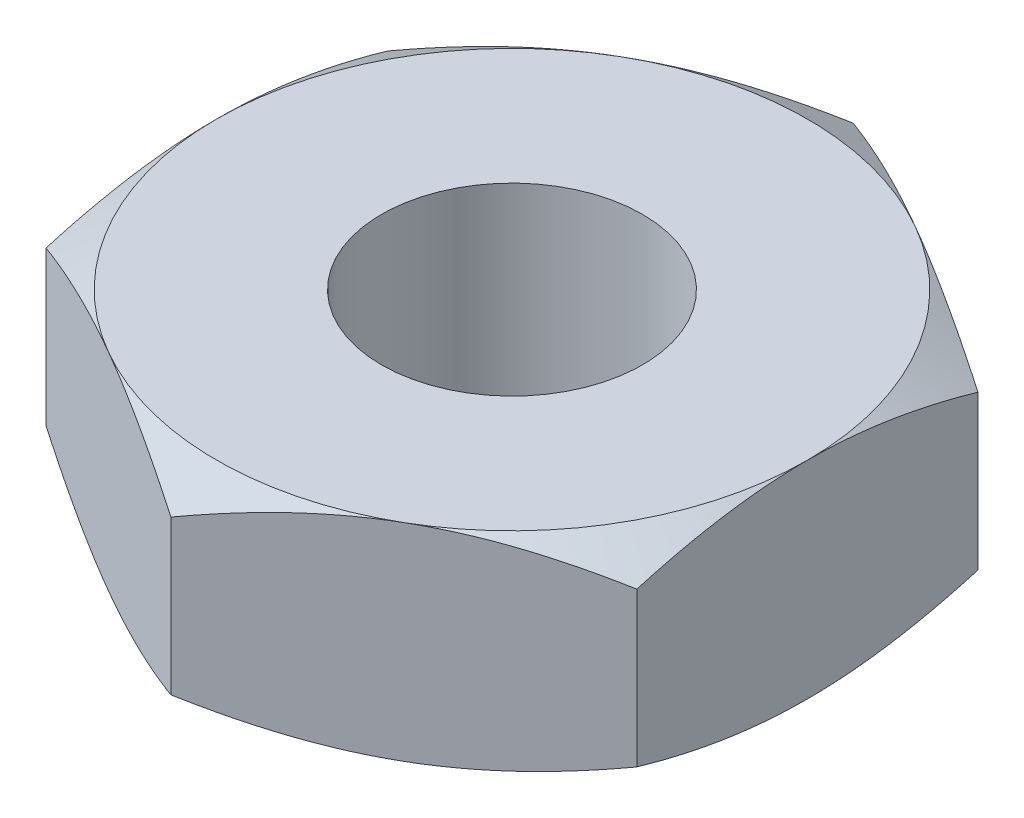
SolidWorks part; units mm, degrees
ref_plane "Front Plane" through (0, 0, 0) normal (0, 0, 1) x (1, 0, 0)
ref_plane "Top Plane" through (0, 0, 0) normal (0, 1, 0) x (1, 0, 0)
ref_plane "Right Plane" through (0, 0, 0) normal (1, 0, 0) x (0, 0, -1)
sketch "Sketch1" plane through (0, 0, 0) normal (0, 1, 0) x (1, 0, 0)
  line L1 (-3.9688, 2.2914) -> (-3.9688, -2.2914)
  line L2 (-3.9688, -2.2914) -> (0, -4.5827)
  line L3 (0, -4.5827) -> (3.9687, -2.2914)
  line L4 (3.9687, -2.2914) -> (3.9688, 2.2914)
  line L5 (3.9688, 2.2914) -> (0, 4.5827)
  line L6 (0, 4.5827) -> (-3.9688, 2.2914)
  circle A0 centre (0, 0) radius 3.9688 construction
  circle A1 centre (0, 0) radius 1.7526
  dimension "Thread Size" = 3.5052
  dimension "Hex" = 7.9375
extrude "Boss-Extrude1" add sketch "Sketch1" along normal mid plane 2.7781
sketch "Sketch2" plane through (0, 1.3891, 0) normal (0, 1, 0) x (1, 0, 0)
  circle A0 centre (0, 0) radius 1.7526 construction
  circle A1 centre (0, 0) radius 1.7526
curve "Helix/Spiral1" [suppressed] pitch 0.7937 height 3.5719 turns 4.5 parameters "Pitch"=0.7937
sketch "Sketch3" plane through (0, 0, 0) normal (1, 0, 0) x (0, 0, -1)
  line L0 (1.237, 1.7859) -> (1.7526, 2.0836)
  line L1 (1.7526, 2.0836) -> (1.7526, 1.3891)
  line L2 (1.7526, 1.3891) -> (1.237, 1.6867)
  line L3 (1.237, 1.6867) -> (1.237, 1.7859)
  line L4 (1.4948, 1.9348) -> (1.4948, 1.5379) construction
  line L5 (1.237, 1.7363) -> (1.7526, 1.7363) construction
  line L6 (1.7526, 1.3891) -> (-1.7526, 1.3891) construction
  dimension "D1" = 60
  dimension "D2" = 0.0992
  dimension "D3" = 0.3969
sweep "Sweep1" [suppressed] add profiles "Sketch3" path "Helix/Spiral1"
sketch "Sketch4" plane through (0, 1.3891, 0) normal (0, 1, 0) x (1, 0, 0)
  circle A1 centre (0, 0) radius 1.7526
  circle A2 centre (0, 0) radius 1.7526
  dimension "D1" = 0
extrude "Cut-Extrude1" [suppressed] cut sketch "Sketch4" along normal through all and the other way through all draft 45
sketch "Sketch5" plane through (0, 1.3891, 0) normal (0, 1, 0) x (1, 0, 0)
  circle A0 centre (0, 0) radius 3.9688 construction
  circle A1 centre (0, 0) radius 3.9688
extrude "Cut-Extrude2" cut sketch "Sketch5" against normal through all draft 60 flip side to cut
mirror "Mirror1" about plane through (0, 0, 0) normal (0, 1, 0) of "Cut-Extrude2", "Cut-Extrude1"
equation "\"D2@Sketch3\" = \"Pitch@Helix/Spiral1\"*.125"
equation "\"D3@Sketch3\" = \"Pitch@Helix/Spiral1\"*.5"
equation "\"D3@Helix/Spiral1\" = \"Height@Boss-Extrude1\"+\"Pitch@Helix/Spiral1\""
